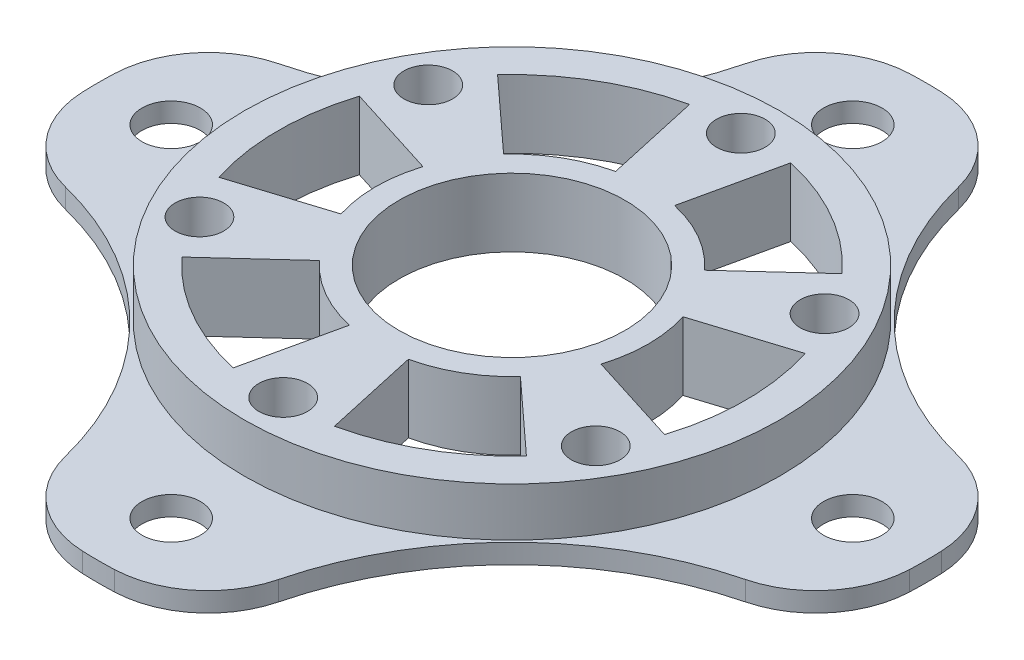
SolidWorks part; units mm, degrees
ref_plane "Front Plane" through (0, 0, 0) normal (0, 0, 1) x (1, 0, 0)
ref_plane "Top Plane" through (0, 0, 0) normal (0, 1, 0) x (1, 0, 0)
ref_plane "Right Plane" through (0, 0, 0) normal (1, 0, 0) x (0, 0, -1)
sketch "Sketch1" plane through (0, 0, 0) normal (0, 1, 0) x (1, 0, 0)
  circle A0 centre (0, 0) radius 27.5
  dimension "D1" = 55
extrude "Boss-Extrude1" add sketch "Sketch1" against normal blind 5
sketch "Sketch2" plane through (0, -5, 0) normal (0, -1, 0) x (1, 0, 0)
  circle A0 centre (0, 0) radius 42.5
  dimension "D1" = 85
extrude "Boss-Extrude2" add sketch "Sketch2" along normal blind 2
sketch "Sketch3" plane through (0, -5, 0) normal (0, 1, 0) x (1, 0, 0)
  circle A0 centre (0, 35) radius 3
  circle A1 centre (35, 0) radius 3
  circle A2 centre (0, -35) radius 3
  circle A3 centre (-35, 0) radius 3
  circle A4 centre (0, 0) radius 42.5 construction
  arc A5 (-10, 41.3068) -> (-41.3068, 10) centre (-42.9586, 42.9586) cw
  arc A6 (41.3068, 10) -> (10, 41.3068) centre (42.9586, 42.9586) cw
  arc A7 (10, -41.3068) -> (41.3068, -10) centre (42.9586, -42.9586) cw
  arc A8 (-41.3068, -10) -> (-10, -41.3068) centre (-42.9586, -42.9586) cw
  circle A10 centre (0, 0) radius 42.5
  circle A11 centre (0, 0) radius 42.5
  point P12 (0, 0)
  point P27 (0, 0)
  circle M3 centre (0, 0) radius 42.5
  dimension "D1" = 6
  dimension "D6" = 33
  dimension "D2" = 35
  dimension "D3" = 4
  dimension "D4" = 10
  dimension "D5" = 10
  dimension "D8" = 0
  dimension "D7" = 4
extrude "Cut-Extrude1" cut sketch "Sketch3" against normal blind 2 contours A5 M3 | A0 | A6 M3 | A1 | A2 | A7 M3 | A8 M3 | A3 region at (0, -5, -35) region at (35, -5, 0) region at (0, -5, 35) region at (-35, -5, 0) region at (-24.9758, -5, -24.9758) region at (24.9758, -5, -24.9758) region at (-24.9758, -5, 24.9758) region at (24.9758, -5, 24.9758)
sketch "Sketch4" plane through (0, 0, 0) normal (0, 1, 0) x (1, 0, 0)
  circle A0 centre (0, 0) radius 11.6
  circle A1 centre (0, 23.5) radius 2.5
  circle A2 centre (20.3516, 11.75) radius 2.5
  circle A3 centre (20.3516, -11.75) radius 2.5
  circle A4 centre (0, -23.5) radius 2.5
  circle A5 centre (-20.3516, -11.75) radius 2.5
  circle A6 centre (-20.3516, 11.75) radius 2.5
  point P18 (0, 0)
  dimension "D1" = 23.2
  dimension "D2" = 5
  dimension "D3" = 23.5
  dimension "D4" = 6
extrude "Cut-Extrude2" cut sketch "Sketch4" against normal through all
sketch "Sketch5" plane through (0, 0, 0) normal (0, 1, 0) x (1, 0, 0)
  line L0 (-17.6947, 16.2142) -> (-10.3219, 9.4583)
  line L1 (-5.1946, 23.4311) -> (-3.0302, 13.6681)
  line L2 (0, 23.537) -> (0, 0) construction
  line L3 (17.6947, 16.2142) -> (10.3219, 9.4583)
  line L4 (5.1946, 23.4311) -> (3.0302, 13.6681)
  line L5 (22.8892, -7.2169) -> (13.352, -4.2099)
  line L6 (22.8892, 7.2169) -> (13.352, 4.2099)
  line L7 (5.1946, -23.4311) -> (3.0302, -13.6681)
  line L8 (17.6947, -16.2142) -> (10.3219, -9.4583)
  line L9 (-17.6947, -16.2142) -> (-10.3219, -9.4583)
  line L10 (-5.1946, -23.4311) -> (-3.0302, -13.6681)
  line L11 (-22.8892, 7.2169) -> (-13.352, 4.2099)
  line L12 (-22.8892, -7.2169) -> (-13.352, -4.2099)
  arc A0 (-10.3219, 9.4583) -> (-3.0302, 13.6681) centre (0, 0) cw
  arc A1 (-17.6947, 16.2142) -> (-5.1946, 23.4311) centre (0, 0) cw
  arc A2 (5.1946, 23.4311) -> (17.6947, 16.2142) centre (0, 0) cw
  arc A3 (3.0302, 13.6681) -> (10.3219, 9.4583) centre (0, 0) cw
  arc A4 (22.8892, 7.2169) -> (22.8892, -7.2169) centre (0, 0) cw
  arc A5 (13.352, 4.2099) -> (13.352, -4.2099) centre (0, 0) cw
  arc A6 (17.6947, -16.2142) -> (5.1946, -23.4311) centre (0, 0) cw
  arc A7 (10.3219, -9.4583) -> (3.0302, -13.6681) centre (0, 0) cw
  arc A8 (-5.1946, -23.4311) -> (-17.6947, -16.2142) centre (0, 0) cw
  arc A9 (-3.0302, -13.6681) -> (-10.3219, -9.4583) centre (0, 0) cw
  arc A10 (-22.8892, -7.2169) -> (-22.8892, 7.2169) centre (0, 0) cw
  arc A11 (-13.352, -4.2099) -> (-13.352, 4.2099) centre (0, 0) cw
  point P30 (0, 0)
  dimension "D2" = 14
  dimension "D3" = 35
  dimension "D4" = 12.5
  dimension "D1" = 10
  dimension "D5" = 6
extrude "Cut-Extrude3" cut sketch "Sketch5" against normal through all
fillet "Fillet1" radius 10 8 edges at (10, -6, -41.3068) (-10, -6, -41.3068) (-41.3068, -6, -10) (-41.3068, -6, 10) (10, -6, 41.3068) (-10, -6, 41.3068) (41.3068, -6, 10) (41.3068, -6, -10)
